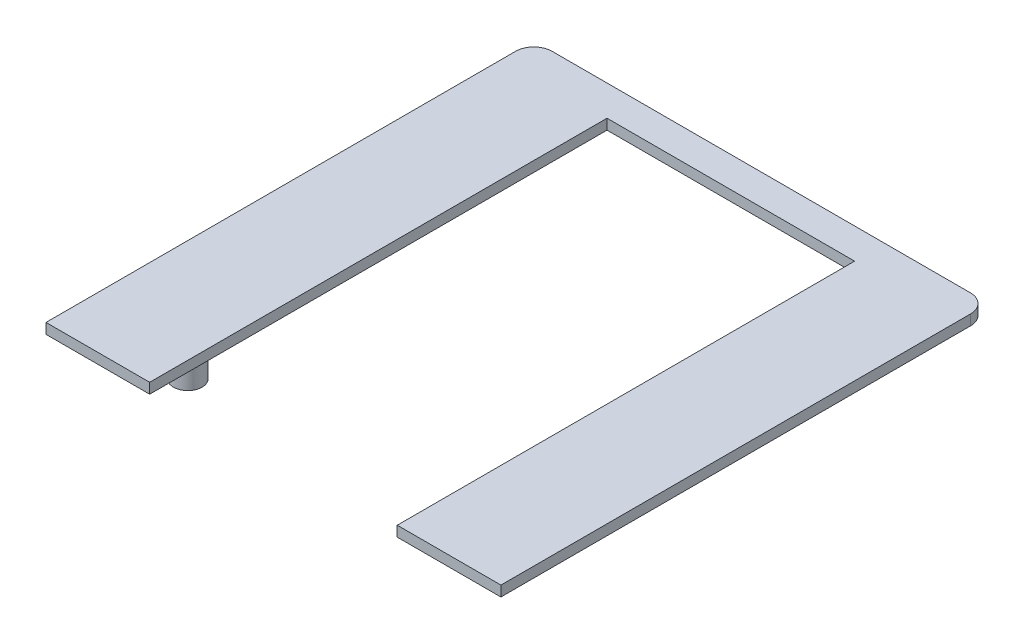
SolidWorks part; units mm, degrees
material "PLA"
ref_plane "Front Plane" through (0, 0, 0) normal (0, 0, 1) x (1, 0, 0)
ref_plane "Top Plane" through (0, 0, 0) normal (0, 1, 0) x (1, 0, 0)
ref_plane "Right Plane" through (0, 0, 0) normal (1, 0, 0) x (0, 0, -1)
sketch "Sketch1" plane through (0, 0, 0) normal (0, 1, 0) x (1, 0, 0)
  line L0 (0, 0) -> (0, 80)
  line L1 (0, 80) -> (37.3, 80)
  line L2 (37.3, 80) -> (37.3, 75)
  line L3 (37.3, 75) -> (17, 75)
  line L4 (17, 75) -> (17, 0)
  line L5 (17, 0) -> (0, 0)
  dimension "D1" = 37.3
  dimension "D2" = 20.3
  dimension "D3" = 5
  dimension "D4" = 80
extrude "Boss-Extrude1" add sketch "Sketch1" along normal blind 1.7
sketch "Sketch2" plane through (0, 0, 0) normal (0, -1, 0) x (-1, 0, 0)
  line L0 (-37.3, 80) -> (0, 80) construction
  line L1 (-17, 0) -> (-17, 75) construction
  line L2 (0, 0) -> (-17, 0) construction
  line L3 (0, 80) -> (0, 0) construction
  circle A0 centre (-13.25, 10) radius 2.35
  circle A1 centre (-8, 72) radius 2.35
  dimension "D2" = 8
  dimension "D3" = 3.75
  dimension "D4" = 10
  dimension "D5" = 4.7
  dimension "D1" = 8
extrude "Boss-Extrude2" add sketch "Sketch2" along normal blind 4.7
fillet "Fillet1" radius 3 1 edges at (0, 0.85, -80)
sketch "Sketch3" plane through (0, 0, 0) normal (0, -1, 0) x (-1, 0, 0)
  line L0 (0, 77) -> (0, 0) construction
  line L1 (-37.3, 80) -> (-3, 80) construction
  circle A0 centre (-13.25, 61.25) radius 2.4
  dimension "D1" = 13.25
  dimension "D2" = 18.75
  dimension "D3" = 4.8
extrude "Cut-Extrude1" cut sketch "Sketch3" against normal blind 1
mirror "Mirror3" about plane through (37.3, 1.7, -80) normal (-1, 0, 0) of bodies 104
